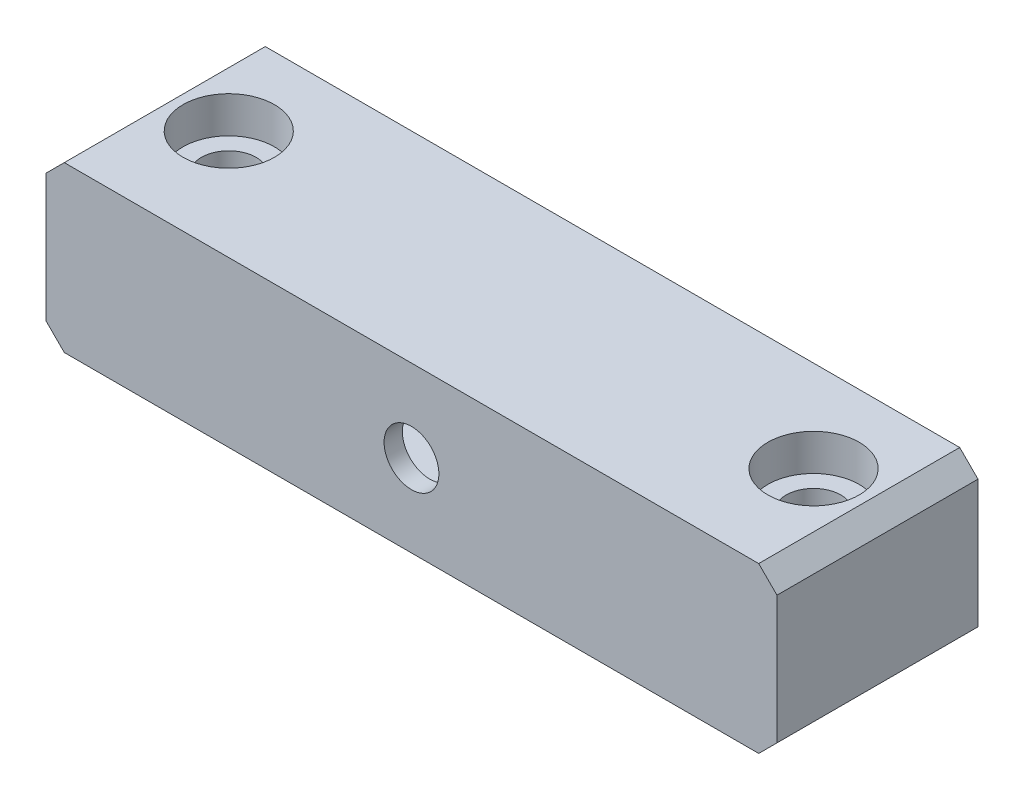
SolidWorks part; units mm, degrees
ref_plane "Front Plane" through (0, 0, 0) normal (0, 0, 1) x (1, 0, 0)
ref_plane "Top Plane" through (0, 0, 0) normal (0, 1, 0) x (1, 0, 0)
ref_plane "Right Plane" through (0, 0, 0) normal (1, 0, 0) x (0, 0, -1)
sketch "Sketch2" plane through (0, 0, 0) normal (0, 0, 1) x (1, 0, 0)
  line L0 (-10, 4.5) -> (10, 4.5)
  line L1 (10, -4.5) -> (-10, -4.5)
  line L2 (-10, 3.5) -> (10, 3.5)
  line L3 (10, -3.5) -> (-10, -3.5)
  line L4 (-10, 4.5) -> (-20, 4.5)
  line L5 (-20, 4.5) -> (-20, -4.5)
  line L6 (-20, -4.5) -> (-10, -4.5)
  line L7 (10, -4.5) -> (20, -4.5)
  line L8 (20, -4.5) -> (20, 4.5)
  line L9 (20, 4.5) -> (10, 4.5)
  arc A2 (10, 3.5) -> (10, -3.5) centre (10, 0) cw
  arc A3 (-10, -3.5) -> (-10, 3.5) centre (-10, 0) cw
  arc A4 (-10, -4.5) -> (-10, 4.5) centre (-10, 0) cw construction
  arc A5 (10, 4.5) -> (10, -4.5) centre (10, 0) cw construction
  point P6 (0, 4.5)
  point P7 (0, -4.5)
  point P20 (0, 3.5)
  dimension "D2" = 3.5
  dimension "D1" = 20
  dimension "D4" = 10
  dimension "D3" = 1
extrude "Boss-Extrude1" add sketch "Sketch2" along normal mid plane 10
extrude "Boss-Extrude2" add sketch "Sketch2<2>" along normal blind 1 from offset 5 contours A3 L3 A2 L2 | L1 L0 L3 A3 L2 A2 region at (0, 4.09, 0) region at (0, 0, 0)
sketch "Sketch2<2>" plane through (0, 0, 0) normal (0, 0, 1) x (1, 0, 0) same geometry as "Sketch2"
sketch "Sketch3" plane through (0, 0, 6) normal (0, 0, 1) x (1, 0, 0)
  circle A0 centre (0, 0) radius 1.5
  dimension "D1" = 3
extrude "Cut-Extrude1" cut sketch "Sketch3" against normal up to next contours A0
sketch "Sketch7" plane through (0, 4.5, 0) normal (0, 1, 0) x (1, 0, 0)
  circle A0 centre (-16, 0) radius 2.5
  circle A1 centre (16, 0) radius 2.5
  circle A2 centre (-16, 0) radius 1.5
  circle A3 centre (16, 0) radius 1.5
  dimension "D1" = 5
  dimension "D2" = 16
  dimension "D4" = 3
  dimension "D3" = 32
extrude "Cut-Extrude2" cut sketch "Sketch7" against normal blind 2 contours A1 | A3 | A2 | A0 A2 | A0 region at (-18.4293, 4.5, 0) region at (13.5707, 4.5, 0) region at (-16, 4.5, 0) region at (16, 4.5, 0)
extrude "Cut-Extrude3" cut sketch "Sketch7<3>" against normal through all contours A2 | A3 region at (-16, 4.5, 0) region at (16, 4.5, 0)
sketch "Sketch7<3>" plane through (0, 4.5, 0) normal (0, 1, 0) x (1, 0, 0) same geometry as "Sketch7"
chamfer "Chamfer1" distance 1 angle 45 4 edges at (-20, -4.5, 0.5) (20, -4.5, 0.5) (20, 4.5, 0.5) (-20, 4.5, 0.5)
